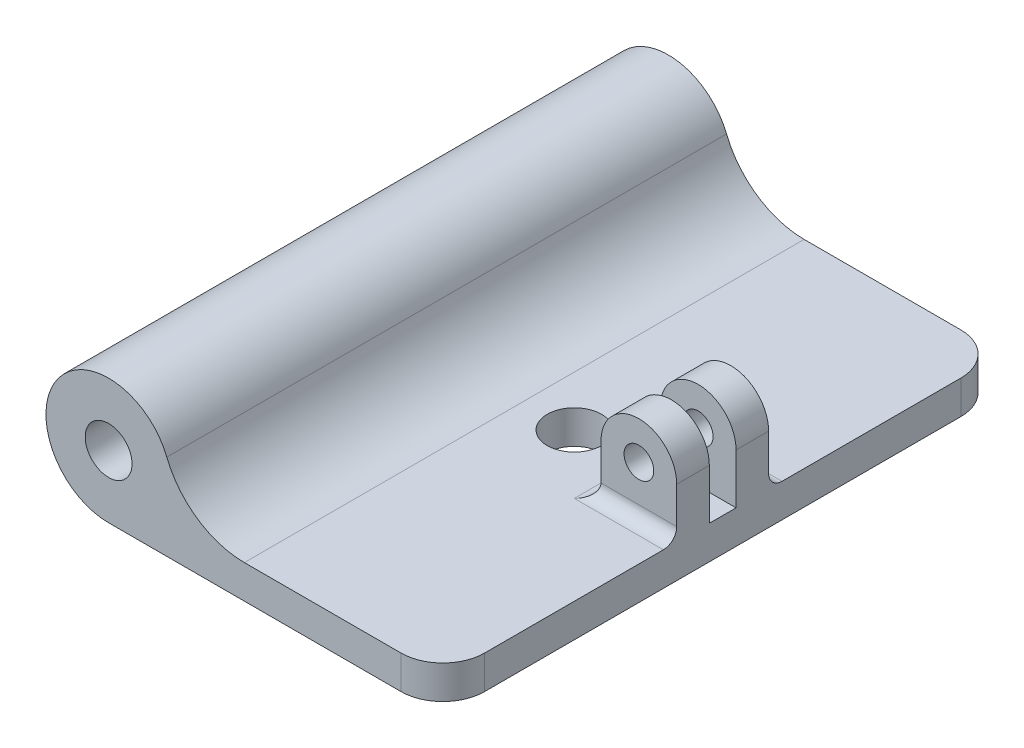
SolidWorks part; units mm, degrees
ref_plane "Front" through (0, 0, 0) normal (0, 0, 1) x (1, 0, 0)
ref_plane "Top" through (0, 0, 0) normal (0, 1, 0) x (1, 0, 0)
ref_plane "Right" through (0, 0, 0) normal (1, 0, 0) x (0, 0, -1)
sketch "Sketch1" plane through (0, 0, 0) normal (0, 0, 1) x (1, 0, 0)
  line L1 (16.2481, -3.5) -> (40, -3.5)
  line L3 (0, -7.5) -> (40, -7.5)
  line L4 (40, -3.5) -> (40, -7.5)
  arc A0 (6.9635, 2.7857) -> (0, -7.5) centre (0, 0) ccw
  arc A1 (6.9635, 2.7857) -> (16.2481, -3.5) centre (16.2481, 6.5) ccw
  circle A2 centre (0, 0) radius 2.8
  dimension "D1" = 15
  dimension "D3" = 10
  dimension "D4" = 5.6
  dimension "D2" = 40
  dimension "D5" = 4
extrude "Boss-Extrude1" add sketch "Sketch1" along normal blind 67
sketch "Sketch2" plane through (0, -3.5, 0) normal (0, 1, 0) x (1, 0, 0)
  line L0 (16.2481, -67) -> (16.2481, 0) construction
  circle A0 centre (22.2481, -33.5) radius 3.25
  point P2 (0, 0)
  point P5 (16.2481, -33.5)
  dimension "D1" = 6.5
  dimension "D2" = 6
extrude "Cut-Extrude1" cut sketch "Sketch2" against normal blind 100
ref_plane "Plane1" through (0, 0, 33.5) normal (0, 0, 1) x (1, 0, 0)
sketch "Sketch3" plane through (0, 0, 33.5) normal (0, 0, 1) x (1, 0, 0)
  line L1 (40, -3.5) -> (30.94, -3.5)
  line L2 (40, -3.5) -> (40, 2.5)
  line L3 (40, 2.5) -> (30.94, 2.5) construction
  line L4 (30.94, -3.5) -> (30.94, 2.5)
  circle A0 centre (35.47, 2.5) radius 4.53
  circle A1 centre (35.47, 2.5) radius 1.778
  point P8 (0, 0)
  dimension "D1" = 3.556
  dimension "D2" = 9.06
  dimension "D3" = 6
extrude "Boss-Extrude2" add sketch "Sketch3" along normal mid plane 11 contours A0 L4 L1 L2 | A0 L3 A1 | L3 A0 A1 region at (35.47, -2.0696, 33.5) region at (35.47, 0.3647, 33.5) region at (35.47, 4.6353, 33.5)
extrude "Cut-Extrude2" cut sketch "Sketch3<3>" against normal mid plane 3.2 contours A0 L4 L1 L2 | A0 L3 A1 | L3 A0 A1 region at (35.47, -2.0696, 33.5) region at (35.47, 0.3647, 33.5) region at (35.47, 4.6353, 33.5)
sketch "Sketch3<3>" plane through (0, 0, 33.5) normal (0, 0, 1) x (1, 0, 0) same geometry as "Sketch3"
fillet "Fillet1" radius 1.6 4 edges at (35.47, -3.5, 28) (30.94, -3.5, 29.95) (30.94, -3.5, 37.05) (35.47, -3.5, 39)
fillet "Fillet2" radius 5 2 edges at (40, -5.5, 0) (40, -5.5, 67)
